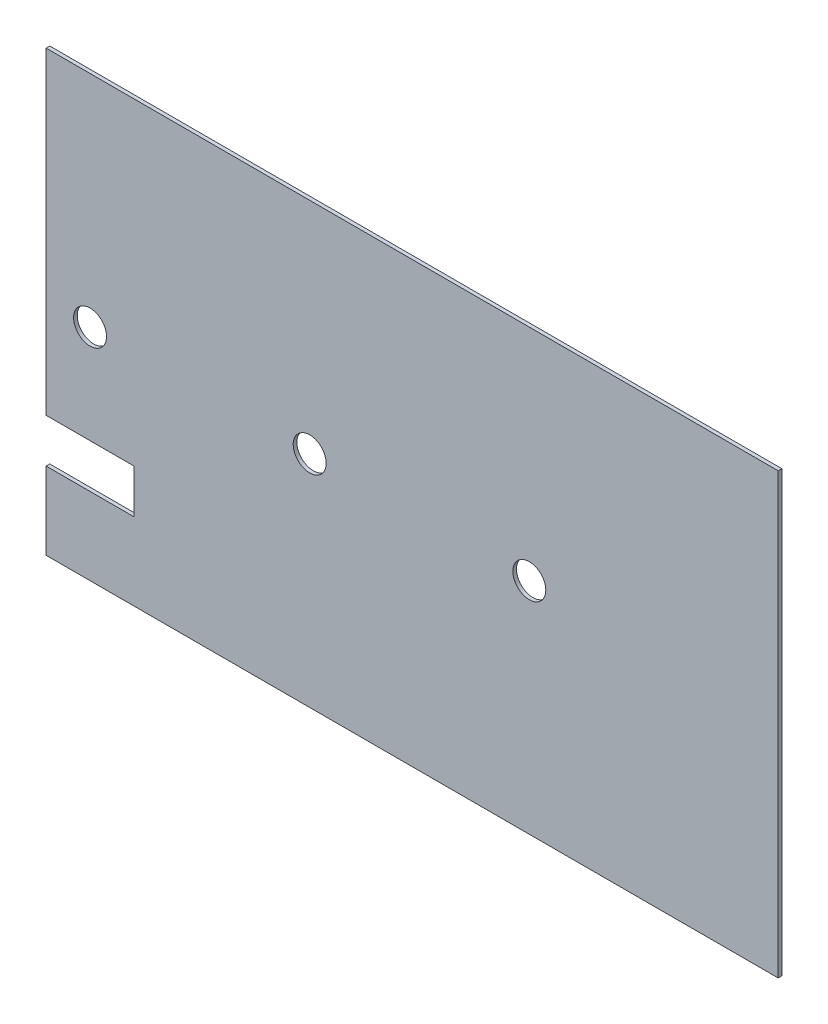
SolidWorks part; units mm, degrees
ref_plane "Front Plane" through (0, 0, 0) normal (0, 0, 1) x (1, 0, 0)
ref_plane "Top Plane" through (0, 0, 0) normal (0, 1, 0) x (1, 0, 0)
ref_plane "Right Plane" through (0, 0, 0) normal (1, 0, 0) x (0, 0, -1)
sketch "Sketch1" plane through (0, 0, 0) normal (0, 0, 1) x (1, 0, 0)
  line L1 (0, 0) -> (685.8, 0)
  line L2 (0, 0) -> (0, 381)
  line L3 (0, 381) -> (685.8, 381)
  line L4 (685.8, 0) -> (685.8, 381)
  dimension "D1" = 381
  dimension "D2" = 685.8
extrude "Boss-Extrude1" add sketch "Sketch1" along normal blind 3.175
sketch "Sketch2" plane through (0, 0, 3.175) normal (0, 0, 1) x (1, 0, 0)
  line L0 (685.8, 0) -> (469.9, 0)
  line L1 (0, 0) -> (685.8, 0) construction
  line L2 (469.9, 0) -> (469.9, 190.5) construction
  line L3 (469.9, 190.5) -> (88.9, 190.5) construction
  circle A0 centre (469.9, 190.5) radius 14.2875
  circle A1 centre (88.9, 190.5) radius 14.2875
  circle A2 centre (279.4, 190.5) radius 14.2875
  dimension "D3" = 28.575
  dimension "D1" = 215.9
  dimension "D2" = 190.5
  dimension "D4" = 381
extrude "Cut-Extrude1" cut sketch "Sketch2" against normal through all contours A1 | A2 | A0
sketch "Sketch3" plane through (0, 0, 3.175) normal (0, 0, 1) x (1, 0, 0)
  line L0 (685.8, 381) -> (0, 381) construction
  line L1 (0, 0) -> (50.8, 0)
  line L2 (0, 0) -> (0, 381)
  line L3 (0, 381) -> (50.8, 381)
  line L4 (50.8, 0) -> (50.8, 381)
  dimension "D1" = 50.8
extrude "Cut-Extrude2" cut sketch "Sketch3" against normal through all
sketch "Sketch5" plane through (0, 0, 3.175) normal (0, 0, 1) x (1, 0, 0)
  line L0 (50.8, 0) -> (50.8, 381) construction
  line L1 (50.8, 67.056) -> (127, 67.056)
  line L2 (50.8, 67.056) -> (50.8, 105.156)
  line L3 (50.8, 105.156) -> (127, 105.156)
  line L4 (127, 67.056) -> (127, 105.156)
  line L5 (50.8, 0) -> (685.8, 0) construction
  dimension "D1" = 67.056
  dimension "D2" = 38.1
  dimension "D3" = 76.2
extrude "Cut-Extrude3" cut sketch "Sketch5" against normal through all
